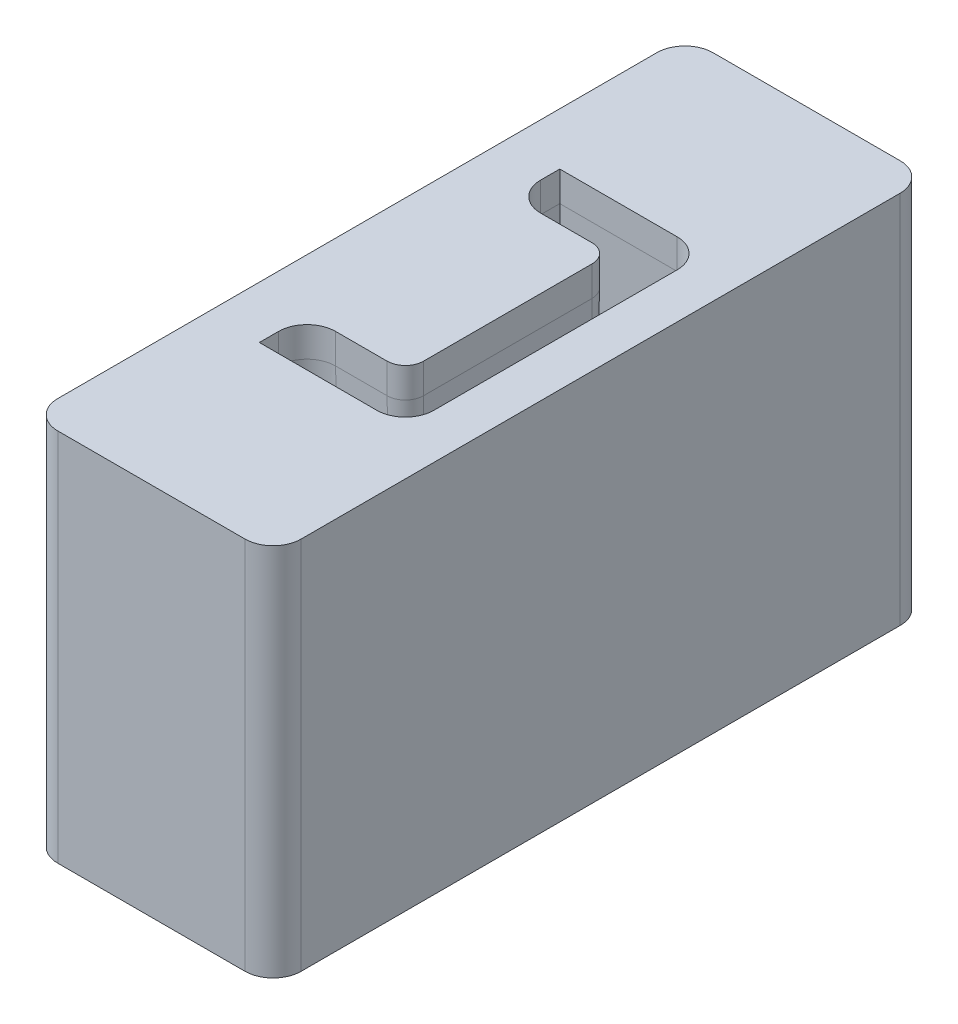
SolidWorks part; units mm, degrees
material "K110"
ref_plane "Front Plane" through (0, 0, 0) normal (0, 0, 1) x (1, 0, 0)
ref_plane "Top Plane" through (0, 0, 0) normal (0, 1, 0) x (1, 0, 0)
ref_plane "Right Plane" through (0, 0, 0) normal (1, 0, 0) x (0, 0, -1)
sketch "Sketch1" plane through (0, 0, 0) normal (0, 1, 0) x (1, 0, 0)
  line L1 (-13, -35) -> (13, -35)
  line L2 (-13, -35) -> (-13, 35)
  line L3 (-13, 35) -> (13, 35)
  line L4 (13, -35) -> (13, 35)
  line L5 (-13, -35) -> (13, 35) construction
  line L6 (-13, 35) -> (13, -35) construction
  point P0 (0, 0)
  dimension "D1" = 70
  dimension "D2" = 26
extrude "Boss-Extrude1" add sketch "Sketch1" against normal blind 40
fillet "Fillet1" radius 3 4 edges at (-13, -20, -35) (13, -20, -35) (-13, -20, 35) (13, -20, 35)
sketch "Sketch9" plane through (0, 0, 0) normal (0, 1, 0) x (1, 0, 0)
  line L72 (3.08, 9) -> (3.08, -9)
  line L73 (1.13, -10.95) -> (-4.37, -10.95)
  line L74 (-7.42, -14) -> (-7.42, -16.05)
  line L75 (-7.42, -16.05) -> (5.13, -16.05)
  line L76 (8.18, -13) -> (8.18, 13)
  line L77 (5.13, 16.05) -> (-7.42, 16.05)
  line L78 (-7.42, 16.05) -> (-7.42, 14)
  line L79 (-4.37, 10.95) -> (1.13, 10.95)
  line L80 (3.08, 9) -> (3.08, -9)
  line L81 (1.13, -10.95) -> (-4.37, -10.95)
  line L82 (-7.42, -14) -> (-7.42, -16.05)
  line L83 (-7.42, -16.05) -> (5.13, -16.05)
  line L84 (8.18, -13) -> (8.18, 13)
  line L85 (5.13, 16.05) -> (-7.42, 16.05)
  line L86 (-7.42, 16.05) -> (-7.42, 14)
  line L87 (-4.37, 10.95) -> (1.13, 10.95)
  arc A54 (3.08, 9) -> (1.13, 10.95) centre (1.13, 9) ccw
  arc A55 (1.13, -10.95) -> (3.08, -9) centre (1.13, -9) ccw
  arc A56 (-4.37, -10.95) -> (-7.42, -14) centre (-4.37, -14) ccw
  arc A57 (5.13, -16.05) -> (8.18, -13) centre (5.13, -13) ccw
  arc A58 (8.18, 13) -> (5.13, 16.05) centre (5.13, 13) ccw
  arc A59 (-7.42, 14) -> (-4.37, 10.95) centre (-4.37, 14) ccw
  arc A60 (3.08, 9) -> (1.13, 10.95) centre (1.13, 9) ccw
  arc A61 (1.13, -10.95) -> (3.08, -9) centre (1.13, -9) ccw
  arc A62 (-4.37, -10.95) -> (-7.42, -14) centre (-4.37, -14) ccw
  arc A63 (5.13, -16.05) -> (8.18, -13) centre (5.13, -13) ccw
  arc A64 (8.18, 13) -> (5.13, 16.05) centre (5.13, 13) ccw
  arc A65 (-7.42, 14) -> (-4.37, 10.95) centre (-4.37, 14) ccw
  dimension "D1" = 0.05
extrude "Cut-Extrude1" cut sketch "Sketch9" against normal up to next
sketch "Sketch11" plane through (0, 0, 0) normal (0, 0, 1) x (1, 0, 0)
  line L0 (8.18, -3.2) -> (8.8223, -40)
  line L2 (-10, -40) -> (10, -40) construction
  line L3 (8.8223, -40) -> (8.18, -40)
  line L4 (8.18, -40) -> (8.18, -3.2)
  line L5 (14.3, 0) -> (-14.3, 0) construction
  line L6 (8.18, -40) -> (8.18, 0) construction
  dimension "D1" = 3.2
  dimension "D2" = 1
sketch "Sketch12" plane through (0, 0, 0) normal (0, 1, 0) x (1, 0, 0)
  line L16 (-7.42, -14) -> (-7.42, -16.05) construction
  line L17 (1.13, -10.95) -> (-4.37, -10.95) construction
  line L18 (-7.42, 16.05) -> (-7.42, 14) construction
  line L19 (-4.37, 10.95) -> (1.13, 10.95) construction
  line L20 (3.08, 9) -> (3.08, -9) construction
  line L21 (-7.42, -16.05) -> (5.13, -16.05) construction
  line L22 (8.18, -13) -> (8.18, 13) construction
  line L23 (5.13, 16.05) -> (-7.42, 16.05) construction
  line L24 (-7.42, -14) -> (-7.42, -16.05)
  line L25 (1.13, -10.95) -> (-4.37, -10.95)
  line L26 (-7.42, 16.05) -> (-7.42, 14)
  line L27 (-4.37, 10.95) -> (1.13, 10.95)
  line L28 (3.08, 9) -> (3.08, -9)
  line L29 (-7.42, -16.05) -> (5.13, -16.05)
  line L30 (8.18, -13) -> (8.18, 13)
  line L31 (5.13, 16.05) -> (-7.42, 16.05)
  arc A12 (-4.37, -10.95) -> (-7.42, -14) centre (-4.37, -14) ccw construction
  arc A13 (1.13, -10.95) -> (3.08, -9) centre (1.13, -9) ccw construction
  arc A14 (-7.42, 14) -> (-4.37, 10.95) centre (-4.37, 14) ccw construction
  arc A15 (3.08, 9) -> (1.13, 10.95) centre (1.13, 9) ccw construction
  arc A16 (5.13, -16.05) -> (8.18, -13) centre (5.13, -13) ccw construction
  arc A17 (8.18, 13) -> (5.13, 16.05) centre (5.13, 13) ccw construction
  arc A18 (-4.37, -10.95) -> (-7.42, -14) centre (-4.37, -14) ccw
  arc A19 (1.13, -10.95) -> (3.08, -9) centre (1.13, -9) ccw
  arc A20 (-7.42, 14) -> (-4.37, 10.95) centre (-4.37, 14) ccw
  arc A21 (3.08, 9) -> (1.13, 10.95) centre (1.13, 9) ccw
  arc A22 (5.13, -16.05) -> (8.18, -13) centre (5.13, -13) ccw
  arc A23 (8.18, 13) -> (5.13, 16.05) centre (5.13, 13) ccw
sweep "Cut-Sweep1" cut profiles "Sketch11" path "Sketch12"
hole_wizard "M8 Tapped Hole1" positions "Sketch16" profile "Sketch14" tap size "M8" standard "ISO"
sketch "Sketch16" plane through (0, -40, 0) normal (0, -1, 0) x (-1, 0, 0)
  line L0 (0, 22) -> (0, -22) construction
  line L2 (0, -35) -> (0, -16.6923) construction
  line L3 (10, -35) -> (-10, -35) construction
  line L5 (0, 35) -> (0, 16.6923) construction
  line L6 (-10, 35) -> (10, 35) construction
  line L10 (8.0623, 16.6923) -> (-5.13, 16.6923) construction
  line L11 (-5.13, -16.6923) -> (8.0623, -16.6923) construction
  point P0 (0, -25.8462)
  point P4 (0, 25.8462)
sketch "Sketch14" plane through (0, -40, 25.8462) normal (1, 0, 0) x (0, 0, -1)
  line L0 (0, 0) -> (0, 24.2929)
  line L1 (0, 24.2929) -> (3.4, 22.25)
  line L2 (3.4, 22.25) -> (3.4, 0)
  line L5 (3.4, 0) -> (0, 0)
  line L10 (0, 24.2929) -> (-3.4, 22.25) construction
  line L11 (0, -6.35) -> (0, 107.95) construction
  dimension "Tap Drill Dia." = 6.8
  dimension "Tap Drill Depth" = 22.25
  dimension "Drill Angle" = 118
cosmetic thread "Hole Thread7"
cosmetic thread "Hole Thread8"
